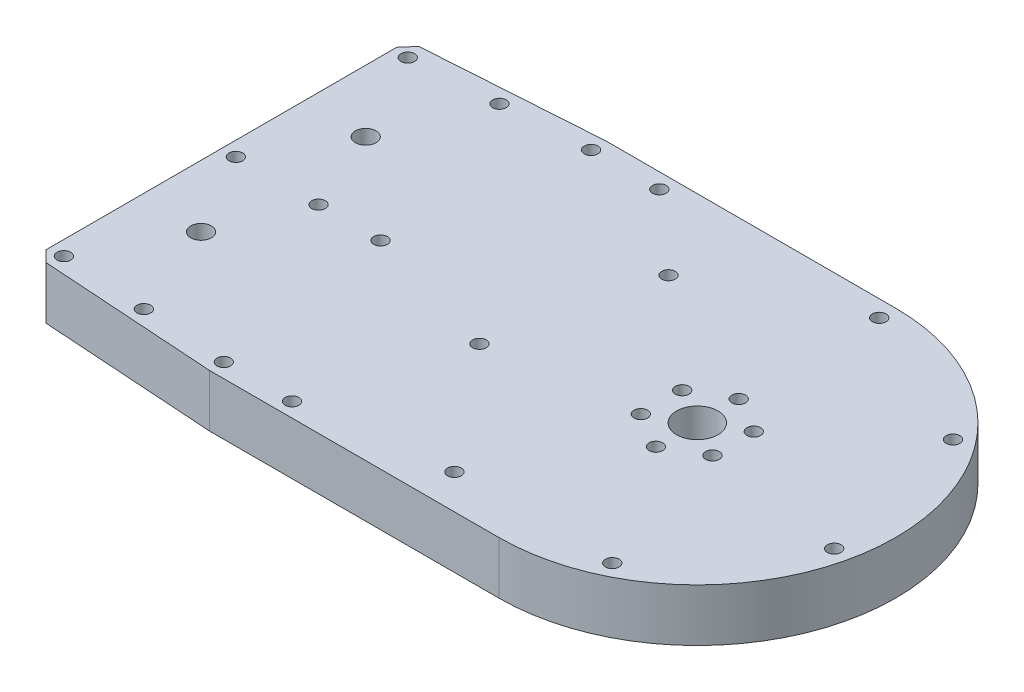
SolidWorks part; units mm, degrees
note: '?' marks a value the reader was unsure of.
material "6061 Alloy"
ref_plane "Front Plane" through (0, 0, 0) normal (0, 0, 1) x (1, 0, 0)
ref_plane "Top Plane" through (0, 0, 0) normal (0, 1, 0) x (1, 0, 0)
ref_plane "Right Plane" through (0, 0, 0) normal (1, 0, 0) x (0, 0, -1)
ref_axis "X Axis" through (-88.99, 0, 0) along (1, 0, 0)?
ref_axis "Y Axiz" through (0, 0, 55) along (0, 0, -1)?
ref_axis "Z Axis" through (0, 55, 0) along (0, -1, 0)?
sketch "Sketch1" plane through (0, 0, 0) normal (0, 1, 0) x (1, 0, 0)
  line L0 (-70, 0) -> (-115, 0) construction
  line L5 (-115, 45) -> (-115, -45)
  line L6 (-70, 48) -> (-70, -48) construction
  line L7 (-70, -48) -> (-115, -45)
  line L8 (-70, 48) -> (0, 48)
  line L9 (-70, 0) -> (0, 0) construction
  line L10 (-70, -48) -> (0, -48)
  line L11 (-70, 48) -> (-115, 45)
  line L12 (0, 0) -> (0, 10) construction
  arc A0 (0, -48) -> (0, 48) centre (0, 0) ccw
  circle A2 centre (0, 0) radius 5
  circle A3 centre (0, 10) radius 1
  circle A4 centre (8.6603, 5) radius 1
  circle A5 centre (8.6603, -5) radius 1
  circle A6 centre (0, -10) radius 1
  circle A7 centre (-8.6603, -5) radius 1
  circle A8 centre (-8.6603, 5) radius 1
  point P26 (0, 0)
  dimension "D1" = 96
  dimension "D2" = 10
  dimension "D3" = 45
  dimension "D5" = 10
  dimension "D7" = 2
  dimension "D4" = 45
  dimension "D6" = 70
  dimension "D8" = 6
extrude "Boss-Extrude1" add sketch "Sketch1" along normal blind 12.7
sketch "Sketch3" plane through (0, 12.7, 0) normal (0, 1, 0) x (1, 0, 0)
  line L0 (0, 0) -> (0, 44) construction
  line L1 (0, -55) -> (0, 55) construction
  line L5 (-48, 0) -> (-48, 44) construction
  line L6 (-48, 0) -> (0, 0) construction
  circle A0 centre (0, 44) radius 1
  circle A1 centre (34.4006, 27.4336) radius 1
  circle A2 centre (42.8968, -9.7909) radius 1
  circle A3 centre (19.0909, -39.6426) radius 1
  circle A4 centre (-19.0909, -39.6426) radius 1
  circle A5 centre (-42.8968, -9.7909) radius 1
  circle A6 centre (-34.4006, 27.4336) radius 1
  point P19 (0, 0)
  point P40 (-48, 0)
  dimension "D2" = 2
  dimension "D1" = 44
  dimension "D3" = 7
extrude "Cut-Extrude1" cut sketch "Sketch3" against normal blind 6.35
hole_wizard "M4x0.7 Tapped Hole1" positions "3DSketch1" profile "Sketch4" tap size "M4x0.7" standard "ANSI Metric" end condition through all
sketch3d "3DSketch1"
  line L0 (-19.0909, 6.35, 39.6426) -> (-19.0909, 12.7, 39.6426) construction
  line L1 (-42.8968, 6.35, 9.7909) -> (-42.8968, 12.7, 9.7909) construction
  line L2 (0, 6.35, -44) -> (0, 12.7, -44) construction
  line L3 (34.4006, 6.35, -27.4336) -> (34.4006, 12.7, -27.4336) construction
  line L4 (42.8968, 6.35, 9.7909) -> (42.8968, 12.7, 9.7909) construction
  line L5 (19.0909, 6.35, 39.6426) -> (19.0909, 12.7, 39.6426) construction
  line L6 (-34.4006, 6.35, -27.4336) -> (-34.4006, 12.7, -27.4336) construction
  point P0 (-19.0909, 12.7, 39.6426)
  point P4 (-42.8968, 12.7, 9.7909)
  point P8 (0, 12.7, -44)
  point P12 (34.4006, 12.7, -27.4336)
  point P16 (42.8968, 12.7, 9.7909)
  point P20 (19.0909, 12.7, 39.6426)
  point P24 (-34.4006, 12.7, -27.4336)
sketch "Sketch4" plane through (-19.0909, 12.7, 39.6426) normal (1, 0, 0) x (0, 0, 1)
  line L0 (0, 0) -> (0, 12.7)
  line L1 (0, 12.7) -> (1.65, 12.7)
  line L2 (1.65, 12.7) -> (1.65, 0)
  line L5 (1.65, 0) -> (0, 0)
  line L11 (0, -6.35) -> (0, 107.95) construction
  dimension "Thru Tap Drill Dia." = 3.3
  dimension "Thru Tap Drill Depth" = 12.7
cosmetic thread "Hole Thread1" parameters "D2"=4
cosmetic thread "Hole Thread2" parameters "D2"=4
cosmetic thread "Hole Thread3" parameters "D2"=4
cosmetic thread "Hole Thread4" parameters "D2"=4
cosmetic thread "Hole Thread5" parameters "D2"=4
cosmetic thread "Hole Thread6" parameters "D2"=4
cosmetic thread "Hole Thread7" parameters "D2"=4
chamfer "Chamfer1" distance 1 angle 45 7 edges at (19.0909, 0, 41.2926) (42.8968, 0, 11.4409) (34.4006, 0, -25.7836) (0, 0, -42.35) (-42.8968, 0, 11.4409) (-19.0909, 0, 41.2926) (-34.4006, 0, -25.7836)
hole_wizard "M4x0.7 Tapped Hole2" positions "3DSketch2" profile "Sketch5" tap size "M4x0.7" standard "ANSI Metric"
sketch3d "3DSketch2"
  line L0 (0, 12.7, -10) -> (0, 0, -10) construction
  line L1 (-8.6603, 12.7, -5) -> (-8.6603, 0, -5) construction
  line L2 (-8.6603, 12.7, 5) -> (-8.6603, 0, 5) construction
  line L3 (0, 12.7, 10) -> (0, 0, 10) construction
  line L4 (8.6603, 12.7, 5) -> (8.6603, 0, 5) construction
  line L5 (8.6603, 12.7, -5) -> (8.6603, 0, -5) construction
  point P0 (0, 12.7, -10)
  point P4 (-8.6603, 12.7, -5)
  point P8 (-8.6603, 12.7, 5)
  point P12 (0, 12.7, 10)
  point P16 (8.6603, 12.7, 5)
  point P20 (8.6603, 12.7, -5)
sketch "Sketch5" plane through (0, 12.7, -10) normal (1, 0, 0) x (0, 0, 1)
  line L0 (0, 0) -> (0, 11.0914)
  line L1 (0, 11.0914) -> (1.65, 10.1)
  line L2 (1.65, 10.1) -> (1.65, 0)
  line L5 (1.65, 0) -> (0, 0)
  line L10 (0, 11.0914) -> (-1.65, 10.1) construction
  line L11 (0, -6.35) -> (0, 107.95) construction
  dimension "Tap Drill Dia." = 3.3
  dimension "Tap Drill Depth" = 10.1
  dimension "Drill Angle" = 118
cosmetic thread "Hole Thread8" parameters "D1"=8, "D2"=4
cosmetic thread "Hole Thread9" parameters "D1"=8, "D2"=4
cosmetic thread "Hole Thread10" parameters "D1"=8, "D2"=4
cosmetic thread "Hole Thread11" parameters "D1"=8, "D2"=4
cosmetic thread "Hole Thread12" parameters "D1"=8, "D2"=4
cosmetic thread "Hole Thread13" parameters "D1"=8, "D2"=4
chamfer "Chamfer2" distance 2.5 angle 45 2 edges at (-115, 6.35, -45) (-115, 6.35, 45)
sketch "Sketch7" plane through (0, 0, 0) normal (0, -1, 0) x (1, 0, 0)
  line L0 (-70, 48) -> (0, 48) construction
  line L1 (-111.5, 41.6786) -> (-70, 44.5) construction
  line L2 (-115, 0.0923) -> (-25.3609, 0.0923) construction
  line L4 (-115, -42.3155) -> (-115, 42.5) construction
  line L5 (-111.5, -41.4941) -> (-70, -44.3155) construction
  line L6 (-115, 42.5) -> (-115, -42.3155) construction
  circle A0 centre (-111.5, 41.6786) radius 0.25
  circle A1 centre (-70, 44.5) radius 0.25
  circle A2 centre (-53.5, 44.5) radius 0.25
  circle A3 centre (-90.75, 43.0893) radius 0.25
  circle A12 centre (-90.75, -42.9048) radius 0.25
  circle A13 centre (-53.5, -44.3155) radius 0.25
  circle A14 centre (-70, -44.3155) radius 0.25
  circle A15 centre (-111.5, -41.4941) radius 0.25
  circle A16 centre (-111.5, 0.0923) radius 0.25
  circle A17 centre (-91.5, 0.0923) radius 0.25
  circle A18 centre (-76.5, 0.0923) radius 0.25
  circle A19 centre (-100, -19.8155) radius 1
  circle A20 centre (-100, 20) radius 1
  point P39 (-115, 20)
  point P40 (-115, -19.8155)
  dimension "D5" = 0.5
  dimension "D6" = 0.5
  dimension "D7" = 0.5
  dimension "D10" = 0.5
  dimension "D12" = 3.5
  dimension "D11" = 0.5
  dimension "D15" = 0.5
  dimension "D16" = 0.5
  dimension "D21" = 2
  dimension "D22" = 2
  dimension "D1" = 3.5
  dimension "D2" = 3.5
  dimension "D3" = 3.5
  dimension "D4" = 0
  dimension "D8" = 3.5
  dimension "D9" = 16.5
  dimension "D13" = 20
  dimension "D14" = 15
  dimension "D17" = 22.5
  dimension "D18" = 22.5
  dimension "D19" = 15
  dimension "D20" = 15
  dimension "D23" = 22.5
  dimension "D24" = 22.5
extrude "Cut-Extrude2" cut sketch "Sketch7" against normal through all
hole_wizard "M4x0.7 Tapped Hole3" positions "3DSketch4" profile "Sketch10" tap size "M4x0.7" standard "ANSI Metric"
sketch3d "3DSketch4"
  line L0 (-90.75, 12.7, 43.0893) -> (-90.75, 0, 43.0893) construction
  line L1 (-111.5, 12.7, 41.6786) -> (-111.5, 0, 41.6786) construction
  line L2 (-70, 12.7, 44.5) -> (-70, 0, 44.5) construction
  line L3 (-53.5, 12.7, 44.5) -> (-53.5, 0, 44.5) construction
  line L4 (-111.5, 12.7, 0.0923) -> (-111.5, 0, 0.0923) construction
  line L5 (-91.5, 12.7, 0.0923) -> (-91.5, 0, 0.0923) construction
  line L6 (-76.5, 12.7, 0.0923) -> (-76.5, 0, 0.0923) construction
  line L7 (-111.5, 12.7, -41.4941) -> (-111.5, 0, -41.4941) construction
  line L8 (-90.75, 12.7, -42.9048) -> (-90.75, 0, -42.9048) construction
  line L9 (-70, 12.7, -44.3155) -> (-70, 0, -44.3155) construction
  line L10 (-53.5, 12.7, -44.3155) -> (-53.5, 0, -44.3155) construction
  point P0 (-90.75, 0, 43.0893)
  point P4 (-111.5, 0, 41.6786)
  point P8 (-70, 0, 44.5)
  point P12 (-53.5, 0, 44.5)
  point P16 (-111.5, 0, 0.0923)
  point P20 (-91.5, 0, 0.0923)
  point P24 (-76.5, 0, 0.0923)
  point P28 (-111.5, 0, -41.4941)
  point P32 (-90.75, 0, -42.9048)
  point P36 (-70, 0, -44.3155)
  point P40 (-53.5, 0, -44.3155)
sketch "Sketch10" plane through (-90.75, 0, 43.0893) normal (1, 0, 0) x (0, 0, -1)
  line L0 (0, 0) -> (0, 16.4914)
  line L1 (0, 16.4914) -> (1.65, 15.5)
  line L2 (1.65, 15.5) -> (1.65, 0)
  line L5 (1.65, 0) -> (0, 0)
  line L10 (0, 16.4914) -> (-1.65, 15.5) construction
  line L11 (0, -6.35) -> (0, 107.95) construction
  dimension "Tap Drill Dia." = 3.3
  dimension "Tap Drill Depth" = 15.5
  dimension "Drill Angle" = 118
cosmetic thread "Hole Thread14" parameters "D1"=8, "D2"=4
cosmetic thread "Hole Thread15" parameters "D1"=8, "D2"=4
cosmetic thread "Hole Thread16" parameters "D1"=8, "D2"=4
cosmetic thread "Hole Thread17" parameters "D1"=8, "D2"=4
cosmetic thread "Hole Thread18" parameters "D1"=8, "D2"=4
cosmetic thread "Hole Thread19" parameters "D1"=8, "D2"=4
cosmetic thread "Hole Thread20" parameters "D1"=8, "D2"=4
cosmetic thread "Hole Thread21" parameters "D1"=8, "D2"=4
cosmetic thread "Hole Thread22" parameters "D1"=8, "D2"=4
cosmetic thread "Hole Thread23" parameters "D1"=8, "D2"=4
cosmetic thread "Hole Thread24" parameters "D1"=8, "D2"=4
hole_wizard "M6x1.0 Tapped Hole1" positions "3DSketch5" profile "Sketch11" tap size "M6x1.0" standard "ANSI Metric"
sketch3d "3DSketch5"
  line L0 (-100, 12.7, 20) -> (-100, 0, 20) construction
  line L1 (-100, 12.7, -19.8155) -> (-100, 0, -19.8155) construction
  point P0 (-100, 0, 20)
  point P4 (-100, 0, -19.8155)
sketch "Sketch11" plane through (-100, 0, 20) normal (1, 0, 0) x (0, 0, -1)
  line L0 (0, 0) -> (0, 18.5022)
  line L1 (0, 18.5022) -> (2.5, 17)
  line L2 (2.5, 17) -> (2.5, 0)
  line L5 (2.5, 0) -> (0, 0)
  line L10 (0, 18.5022) -> (-2.5, 17) construction
  line L11 (0, -6.35) -> (0, 107.95) construction
  dimension "Tap Drill Dia." = 5
  dimension "Tap Drill Depth" = 17
  dimension "Drill Angle" = 118
cosmetic thread "Hole Thread25" parameters "D1"=12, "D2"=6
cosmetic thread "Hole Thread26" parameters "D1"=12, "D2"=6
